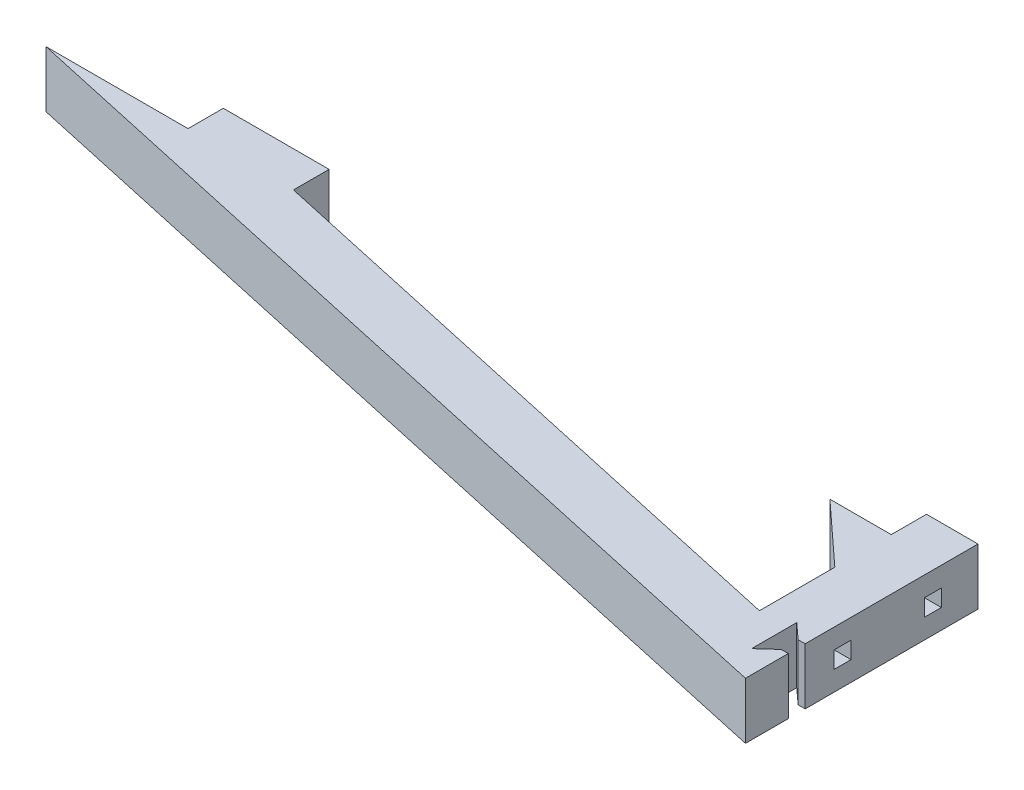
SolidWorks part; units mm, degrees
ref_plane "Přední rovina" through (0, 0, 0) normal (0, 0, 1) x (1, 0, 0)
ref_plane "Horní rovina" through (0, 0, 0) normal (0, 1, 0) x (1, 0, 0)
ref_plane "Pravá rovina" through (0, 0, 0) normal (1, 0, 0) x (0, 0, -1)
sketch "Skica2" plane through (0, 0, 0) normal (0, 1, 0) x (1, 0, 0)
  line L13 (0, 0) -> (0, -32.97)
  line L14 (0, -32.97) -> (-127.1408, -5)
  line L18 (-107, 0) -> (-92, 0)
  line L19 (-92, 0) -> (-92, -5.0514)
  line L20 (-92, -5.0514) -> (-7.3, -23.6847)
  line L21 (-7.3, -23.6847) -> (-7.3, 0)
  line L22 (-7.3, 0) -> (0, 0)
  line L24 (-127.1408, -5) -> (-107, -5)
  line L25 (-107, 0) -> (-107, -5)
  dimension "D1" = 32.97
  dimension "D2" = 77.593
  dimension "D3" = 5
  dimension "D4" = 15
  dimension "D5" = 7.3
  dimension "D7" = 7.5
  dimension "D8" = 84.7
extrude "Přidat vysunutím1" add sketch "Skica2" along normal blind 8
sketch "Skica3" plane through (0, 8, 0) normal (0, 1, 0) x (1, 0, 0)
  line L6 (0, -24.5) -> (-1, -24.5)
  line L7 (0, -32.97) -> (0, 0) construction
  line L8 (-1, -24.5) -> (-3.2, -22.5)
  line L9 (-3.2, -22.5) -> (-3.2, -28.9)
  line L10 (-3.2, -28.9) -> (-1, -26.9)
  line L11 (-1, -26.9) -> (0, -26.9)
  line L12 (0, -26.9) -> (0, -24.5)
  line L13 (0, 0) -> (-7.3, 0) construction
  dimension "D1" = 1
  dimension "D2" = 1
  dimension "D3" = 6.4
  dimension "D4" = 2.4
  dimension "D5" = 3.2
  dimension "D6" = 2
  dimension "40" = 22.5
extrude "Odebrat vysunutím1" cut sketch "Skica3" against normal through all
sketch "Skica5" plane through (0, 8, 0) normal (0, 1, 0) x (1, 0, 0)
  line L10 (0, -24.5) -> (0, 0) construction
  line L11 (0, -5) -> (-16, -5)
  line L12 (0, -5) -> (0, -13)
  line L13 (0, -13) -> (-16, -13)
  line L14 (-16, -5) -> (-16, -13)
  line L15 (0, 0) -> (-7.3, 0) construction
  dimension "D1" = 5
  dimension "D2" = 8
  dimension "D3" = 16
extrude "Přidat vysunutím2" add sketch "Skica5" against normal blind 8
sketch "Skica7" plane through (0, 0, 0) normal (0, -1, 0) x (1, 0, 0)
  line L3 (-16, 5) -> (-16, 13)
  line L4 (-16, 13) -> (-7.3, 13)
  line L5 (-7.3, 13) -> (-16, 5)
extrude "Odebrat vysunutím4" cut sketch "Skica7" against normal through all
sketch "Skica4" plane through (0, 0, 0) normal (1, 0, 0) x (0, 0, -1)
  line L0 (-24.5, 8) -> (0, 8) construction
  line L5 (-20.4, 5.2) -> (-18, 5.2)
  line L6 (-20.4, 5.2) -> (-20.4, 2.8)
  line L7 (-20.4, 2.8) -> (-18, 2.8)
  line L8 (-18, 5.2) -> (-18, 2.8)
  line L9 (-7.6, 5.2) -> (-5.2, 5.2)
  line L10 (-7.6, 5.2) -> (-7.6, 2.8)
  line L11 (-7.6, 2.8) -> (-5.2, 2.8)
  line L12 (-5.2, 5.2) -> (-5.2, 2.8)
  line L14 (0, 8) -> (0, 0) construction
  dimension "D3" = 2.4
  dimension "D4" = 2.4
  dimension "D5" = 2.4
  dimension "D6" = 2.4
  dimension "D7" = 2.8
  dimension "D8" = 2.8
  dimension "D10" = 5.2
  dimension "D11" = 10.4
extrude "Odebrat vysunutím2" cut sketch "Skica4" against normal blind 4.4
